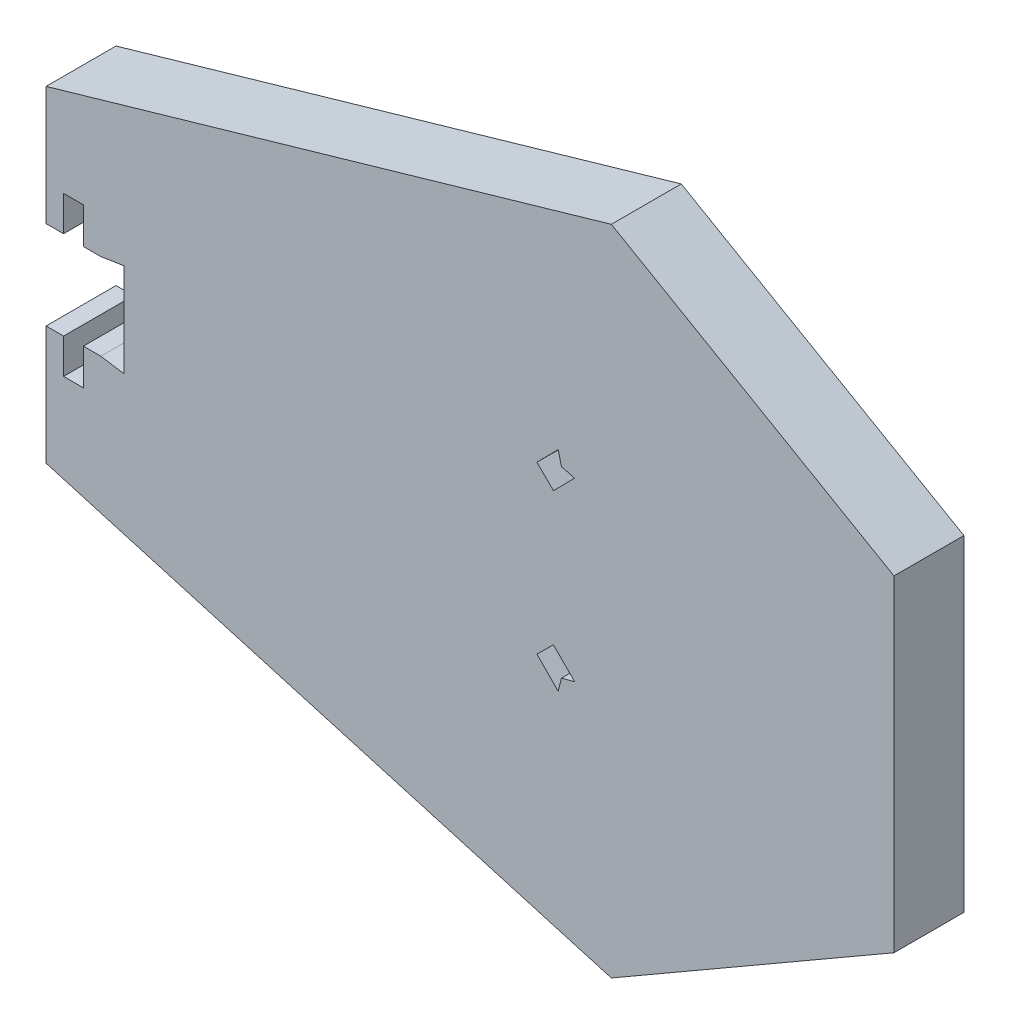
SolidWorks part; units mm, degrees
ref_plane "Front Plane" through (0, 0, 0) normal (0, 0, 1) x (1, 0, 0)
ref_plane "Top Plane" through (0, 0, 0) normal (0, 1, 0) x (1, 0, 0)
ref_plane "Right Plane" through (0, 0, 0) normal (1, 0, 0) x (0, 0, -1)
sketch "Sketch1" plane through (0, 0, 0) normal (0, 0, 1) x (1, 0, 0)
  line L0 (31.2231, 14) -> (6.9744, 28) construction
  line L1 (31.2231, -14) -> (31.2231, 14) construction
  line L2 (6.9744, -28) -> (31.2231, -14) construction
  line L3 (6.9744, -28) -> (-41.5231, -14) construction
  line L4 (-41.5231, 14) -> (-41.5231, -14) construction
  line L5 (-41.5231, 14) -> (6.9744, 28) construction
  line L6 (31.2231, 14) -> (6.9744, 28)
  line L7 (31.2231, -14) -> (31.2231, 14)
  line L8 (6.9744, -28) -> (31.2231, -14)
  line L9 (6.9744, -28) -> (-41.5231, -14)
  line L10 (-41.5231, 14) -> (-41.5231, -14)
  line L11 (-41.5231, 14) -> (6.9744, 28)
  line L18 (-41.5231, 3.7) -> (-36.8231, 3.7)
  line L19 (-36.8231, 3.7) -> (-34.8231, 4.0157)
  line L20 (-16.8732, 6.8495) -> (-36.8231, 3.7) construction
  line L21 (-34.8231, 4.0157) -> (-34.8231, -4.0157)
  line L23 (-16.8732, -6.8495) -> (-36.8231, -3.7) construction
  line L24 (-34.8231, -4.0157) -> (-36.8231, -3.7)
  line L25 (-36.8231, -3.7) -> (-41.5231, -3.7)
  line L26 (-39.9231, 3.7) -> (-38.3231, 3.7) construction
  line L27 (-36.8231, 3.7) -> (-36.8231, 1.4) construction
  line L28 (-41.5231, 0) -> (31.2231, 0) construction
  line L29 (2.4087, -8.9791) -> (0.5844, -7.1276)
  line L30 (0.5844, -7.1276) -> (2.009, -5.7239)
  line L31 (2.009, -5.7239) -> (3.8193, -7.5613)
  line L32 (3.8193, -7.5613) -> (2.7004, -7.8504)
  line L33 (2.7004, 7.8504) -> (2.4087, 8.9791)
  line L34 (2.7004, 7.8504) -> (2.4087, 8.9791)
  line L35 (3.8193, 7.5613) -> (2.7004, 7.8504)
  line L36 (3.8193, 7.5613) -> (2.7004, 7.8504)
  line L37 (2.009, 5.7239) -> (3.8193, 7.5613)
  line L38 (2.009, 5.7239) -> (3.8193, 7.5613)
  line L39 (0.5844, 7.1276) -> (2.009, 5.7239)
  line L40 (0.5844, 7.1276) -> (2.009, 5.7239)
  line L41 (2.4087, 8.9791) -> (0.5844, 7.1276)
  line L42 (2.4087, 8.9791) -> (0.5844, 7.1276)
  line L43 (2.7004, -7.8504) -> (2.4087, -8.9791)
  dimension "D1" = 2
  dimension "D2" = 0
extrude "Boss-Extrude1" add sketch "Sketch1" along normal blind 6 contours L28 L21 L24 L25 L10 L9 L8 L7 | L21 L28 L7 L6 L11 L10 L18 L19 region at (-3.2455, 11.0511, 0) region at (-3.2455, -11.0511, 0)
sketch "Sketch2" plane through (0, 0, 6) normal (0, 0, 1) x (1, 0, 0)
  line L20 (-41.6231, -3.4275) -> (-41.6231, -3.8)
  line L21 (-41.6231, -3.8) -> (-40.0231, -3.8)
  line L22 (-40.0231, -3.8) -> (-40.0231, -6.8)
  line L23 (-40.0231, -6.8) -> (-38.3231, -6.8)
  line L24 (-38.3231, -6.8) -> (-38.3231, 6.8)
  line L25 (-38.3231, 6.8) -> (-40.0231, 6.8)
  line L26 (-40.0231, 6.8) -> (-40.0231, 3.8)
  line L27 (-40.0231, 3.8) -> (-41.6231, 3.8)
  line L28 (-41.6231, 3.8) -> (-41.6231, 3.4275)
  line L29 (-41.6231, 3.4275) -> (-41.6231, -3.4275)
  line L30 (-41.6231, -3.4275) -> (-41.6231, -3.8)
  line L31 (-41.6231, -3.8) -> (-40.0231, -3.8)
  line L32 (-40.0231, -3.8) -> (-40.0231, -6.8)
  line L33 (-40.0231, -6.8) -> (-38.3231, -6.8)
  line L34 (-38.3231, -6.8) -> (-38.3231, 6.8)
  line L35 (-38.3231, 6.8) -> (-40.0231, 6.8)
  line L36 (-40.0231, 6.8) -> (-40.0231, 3.8)
  line L37 (-40.0231, 3.8) -> (-41.6231, 3.8)
  line L38 (-41.6231, 3.8) -> (-41.6231, 3.4275)
  line L39 (-41.6231, 3.4275) -> (-41.6231, -3.4275)
  dimension "D1" = 0.1
extrude "Cut-Extrude1" cut sketch "Sketch2" against normal through all
sketch "Sketch3" plane through (0, 0, 6) normal (0, 0, 1) x (1, 0, 0)
  line L0 (6.9744, 28) -> (6.9744, -28) construction
  line L1 (31.2231, 0) -> (6.9744, 0) construction
  line L2 (31.2231, -14) -> (31.2231, 14) construction
ref_plane "Plane1" through (0, 0, 0) normal (0, 1, 0) x (-1, 0, 0)
